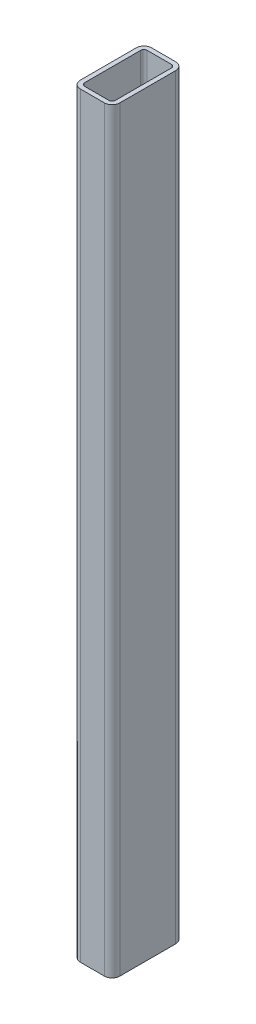
SolidWorks part; units mm, degrees
ref_plane "Спереди" through (0, 0, 0) normal (0, 0, 1) x (1, 0, 0)
ref_plane "Сверху" through (0, 0, 0) normal (0, 1, 0) x (1, 0, 0)
ref_plane "Справа" through (0, 0, 0) normal (1, 0, 0) x (0, 0, -1)
sketch "Эскиз1" plane through (0, 0, 0) normal (0, 1, 0) x (1, 0, 0)
  line L1 (-5.5, 14.25) -> (5.5, 14.25)
  line L2 (-7, 12.75) -> (-7, -12.75)
  line L3 (-5.5, -14.25) -> (5.5, -14.25)
  line L4 (7, 12.75) -> (7, -12.75)
  line L5 (-7, 14.25) -> (7, -14.25) construction
  line L6 (-7, -14.25) -> (7, 14.25) construction
  arc A0 (7, 12.75) -> (5.5, 14.25) centre (5.5, 12.75) ccw
  arc A1 (-5.5, 14.25) -> (-7, 12.75) centre (-5.5, 12.75) ccw
  arc A2 (-5.5, -14.25) -> (-7, -12.75) centre (-5.5, -12.75) cw
  arc A3 (7, -12.75) -> (5.5, -14.25) centre (5.5, -12.75) cw
  point P0 (0, 0)
  dimension "D1" = 1.5
  dimension "D2" = 1.5
  dimension "D3" = 14
  dimension "D4" = 28.5
extrude "Вытянуть-Тонкостенный1" add sketch "Эскиз1" along normal blind 345 thin thin type one direction wall 2
